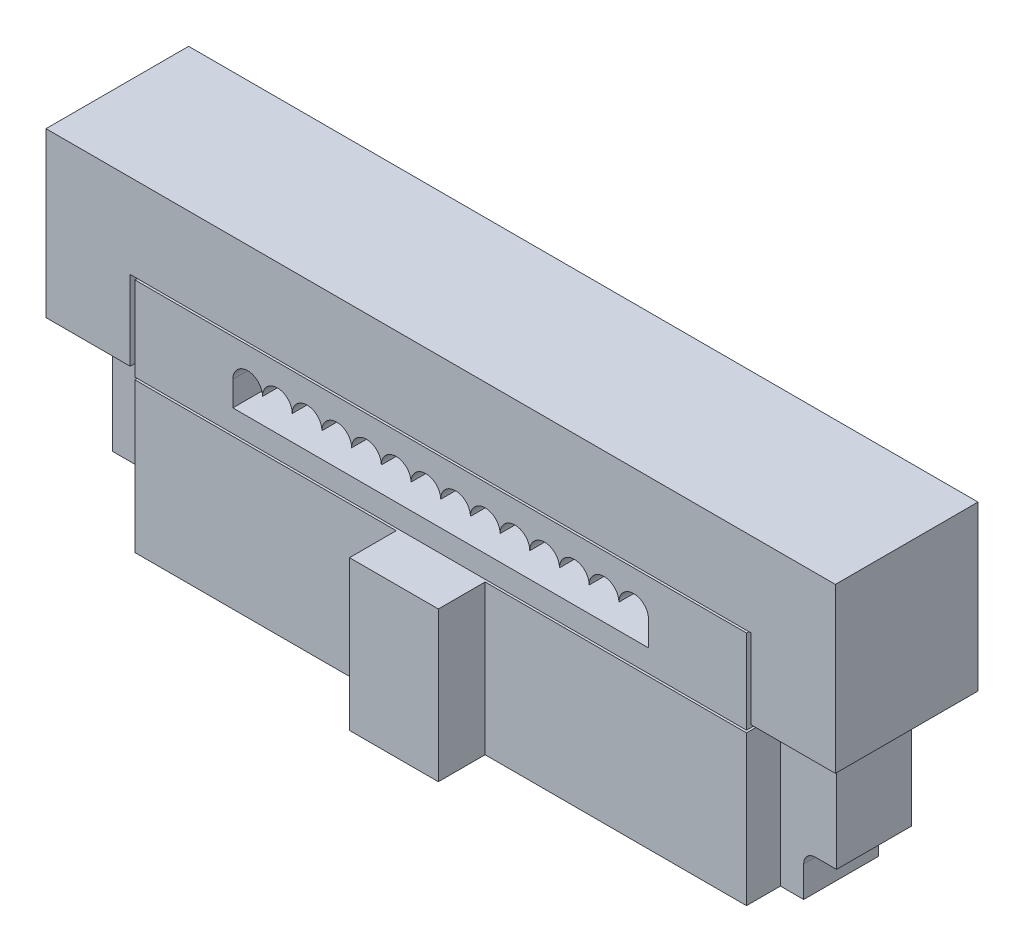
SolidWorks part; units mm, degrees
ref_plane "Front Plane" through (0, 0, 0) normal (0, 0, 1) x (1, 0, 0)
ref_plane "Top Plane" through (0, 0, 0) normal (0, 1, 0) x (1, 0, 0)
ref_plane "Right Plane" through (0, 0, 0) normal (1, 0, 0) x (0, 0, -1)
sketch "Sketch1" plane through (0, 0, 0) normal (0, 0, 1) x (1, 0, 0)
  line L0 (-7.6367, 0.0053) -> (-7.6367, 3.2053) construction
  line L2 (-6.54, 0) -> (6.54, 0)
  line L3 (-6.54, 0) -> (-6.54, 3.2)
  line L4 (-6.54, 3.2) -> (6.54, 3.2)
  line L5 (6.54, 0) -> (6.54, 3.2)
  dimension "D1" = 3.2
  dimension "D2" = 13.08
  dimension "D3" = 3.2
extrude "Boss-Extrude1" add sketch "Sketch1" against normal blind 3.05
sketch "Sketch2" plane through (0, 0, 0) normal (0, 0, 1) x (1, 0, 0)
  line L0 (-12.3527, 6.6596) -> (-12.303, 10.0361) construction
  line L1 (-6.5164, -0.0222) -> (-6.5164, 3.1778) construction
  line L2 (6.54, 0) -> (7.0375, 0)
  line L3 (7.0375, 0) -> (7.0375, 0.6598)
  line L4 (7.2875, 0.9098) -> (7.74, 0.9098)
  line L5 (7.74, 0.9098) -> (7.74, 6.4)
  line L6 (7.74, 6.4) -> (6.9412, 6.4)
  line L7 (6.9412, 6.4) -> (6.9412, 3.1787)
  line L8 (6.9412, 3.1787) -> (6.54, 3.2)
  line L9 (6.54, 3.2) -> (6.54, 0)
  line L10 (0, 7.2169) -> (0, -1.9094) construction
  line L11 (-6.54, 3.2) -> (-6.54, 0)
  line L12 (-6.9412, 3.1787) -> (-6.54, 3.2)
  line L13 (-6.9412, 6.4) -> (-6.9412, 3.1787)
  line L14 (-7.74, 6.4) -> (-6.9412, 6.4)
  line L15 (-7.74, 0.9098) -> (-7.74, 6.4)
  line L16 (-7.2875, 0.9098) -> (-7.74, 0.9098)
  line L17 (-7.0375, 0) -> (-7.0375, 0.6598)
  line L18 (-6.54, 0) -> (-7.0375, 0)
  arc A0 (7.0375, 0.6598) -> (7.2875, 0.9098) centre (7.2875, 0.6598) cw
  arc A1 (-7.0375, 0.6598) -> (-7.2875, 0.9098) centre (-7.2875, 0.6598) ccw
  dimension "D2" = 0.25
  dimension "D1" = 3.2
  dimension "D3" = 6.4
  dimension "D4" = 1.2
extrude "Boss-Extrude2" add sketch "Sketch2" against normal blind 1.6 from offset 0.725 offset against normal yes
sketch "Sketch4" plane through (0, 0, 0) normal (0, 0, 1) x (1, 0, 0)
  line L0 (-6.54, 0) -> (6.54, 0) construction
  line L1 (-0.95, 3.2) -> (0.95, 3.2)
  line L2 (-0.95, 3.2) -> (-0.95, 0)
  line L3 (-0.95, 0) -> (0.95, 0)
  line L4 (0.95, 3.2) -> (0.95, 0)
  line L5 (-0.95, 3.2) -> (0.95, 0) construction
  line L6 (-0.95, 0) -> (0.95, 3.2) construction
  line L7 (6.54, 3.2) -> (-6.54, 3.2) construction
  point P0 (0, 1.6)
  dimension "D1" = 1.9
extrude "Polarizing key" add sketch "Sketch4" along normal blind 1
sketch "Sketch5" plane through (0, 0, 0) normal (0, 0, 1) x (1, 0, 0)
  line L0 (6.54, 0) -> (6.54, 3.2) construction
  line L1 (-6.54, 3.2) -> (6.973, 3.2) construction
  line L2 (-6.54, 3.25) -> (-6.54, 5.05)
  line L3 (-6.54, 5.05) -> (6.54, 5.05)
  line L4 (6.54, 3.25) -> (6.54, 5.05)
  line L5 (-4.445, 4.2562) -> (4.445, 4.2562) construction
  line L6 (-4.445, 3.7262) -> (4.445, 3.7262)
  line L7 (-4.445, 3.7262) -> (-4.445, 4.5738) construction
  line L8 (-4.445, 4.5738) -> (4.445, 4.5738) construction
  line L9 (4.445, 3.7262) -> (4.445, 4.5738) construction
  line L10 (-4.445, 4.2562) -> (-3.81, 4.2562) construction
  line L11 (4.445, 4.2562) -> (4.445, 3.7262)
  line L12 (-4.445, 4.2562) -> (-4.445, 3.7262)
  line L13 (-6.54, 3.25) -> (6.54, 3.25)
  line L14 (-4.445, 4.5738) -> (4.445, 3.7262) construction
  arc A0 (-4.445, 4.2562) -> (-3.81, 4.2562) centre (-4.1275, 4.2562) cw
  arc A1 (-3.81, 4.2562) -> (-3.175, 4.2562) centre (-3.4925, 4.2562) cw
  arc A2 (-3.175, 4.2562) -> (-2.54, 4.2562) centre (-2.8575, 4.2562) cw
  arc A3 (-2.54, 4.2562) -> (-1.905, 4.2562) centre (-2.2225, 4.2562) cw
  arc A4 (-1.905, 4.2562) -> (-1.27, 4.2562) centre (-1.5875, 4.2562) cw
  arc A5 (-1.27, 4.2562) -> (-0.635, 4.2562) centre (-0.9525, 4.2562) cw
  arc A6 (-0.635, 4.2562) -> (0, 4.2562) centre (-0.3175, 4.2562) cw
  arc A7 (0, 4.2562) -> (0.635, 4.2562) centre (0.3175, 4.2562) cw
  arc A8 (0.635, 4.2562) -> (1.27, 4.2562) centre (0.9525, 4.2562) cw
  arc A9 (1.27, 4.2562) -> (1.905, 4.2562) centre (1.5875, 4.2562) cw
  arc A10 (1.905, 4.2562) -> (2.54, 4.2562) centre (2.2225, 4.2562) cw
  arc A11 (2.54, 4.2562) -> (3.175, 4.2562) centre (2.8575, 4.2562) cw
  arc A12 (3.175, 4.2562) -> (3.81, 4.2562) centre (3.4925, 4.2562) cw
  arc A13 (3.81, 4.2562) -> (4.445, 4.2562) centre (4.1275, 4.2562) cw
  point P11 (0, 3.7262)
  point P12 (4.445, 4.15)
  point P17 (6.54, 4.15)
  point P18 (0, 4.2562)
  point P62 (0, 4.15)
  line M16 (-0.95, 3.2) -> (-6.54, 3.2)
  dimension "D3" = 0.3175
  dimension "D1" = 1.9
  dimension "D2" = 0.53
  dimension "D5" = 0.635
  dimension "D6" = 0.05
  dimension "D4" = 14
extrude "Cable clip" add sketch "Sketch5" against normal up to surface (3.05 mm away) contours L1 L4 L3 L2 A12 A13 L11 L6 L12 A0 A1 A2 A3 A4 A5 A6 A7 A8 A9 A10 A11 M16 region at (-6.408, 4.15, 0) up to face at (0, 1.6, -3.05)
sketch "Sketch6" plane through (0, 0, 0) normal (0, 0, 1) x (1, 0, 0)
  line L0 (-8.44, 3.4) -> (-6.64, 3.4)
  line L1 (-6.64, 3.4) -> (-6.64, 5.1)
  line L2 (-6.64, 5.1) -> (6.64, 5.1)
  line L3 (6.64, 5.1) -> (6.64, 3.4)
  line L4 (6.64, 3.4) -> (8.44, 3.4)
  line L5 (8.44, 3.4) -> (8.44, 6.9)
  line L6 (8.44, 6.9) -> (-8.44, 6.9)
  line L7 (-8.44, 6.9) -> (-8.44, 3.4)
  line L8 (-6.54, 3.25) -> (-6.54, 5.05) construction
  line L9 (-6.54, 5.05) -> (6.54, 5.05) construction
  line L10 (7.74, 6.4) -> (6.9412, 6.4) construction
  point P8 (0, 5.1)
  dimension "D1" = 16.88
  dimension "D2" = 0.1
  dimension "D3" = 3.5
  dimension "D4" = 0.05
  dimension "D5" = 0.5
extrude "Boss-Extrude5" add sketch "Sketch6" against normal up to surface (3.05 mm away) up to face at (0, 1.6, -3.05)
ref_axis "Cable mating axis" through (0, 4.15, 0) along (0, 0, 1)
equation "\"D19@Boss-Extrude2\"=(3.05-1.6)/2"
